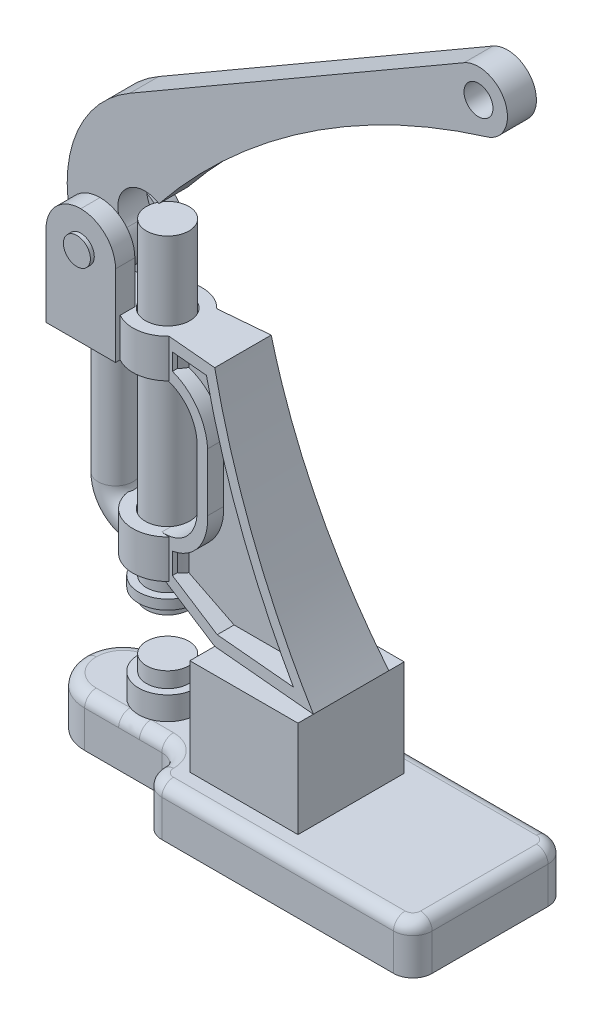
SolidWorks part; units mm, degrees
note: The reader was unsure of these and kept them because the rebuilt part matched: shared geometry of "Sketch8<2>".
other "Base Frame"
other "Sliding Rod"
other "Handle"
other "Pin"
ref_plane "Front Plane" through (0, 0, 0) normal (0, 0, 1) x (1, 0, 0)
ref_plane "Top Plane" through (0, 0, 0) normal (0, 1, 0) x (1, 0, 0)
ref_plane "Right Plane" through (0, 0, 0) normal (1, 0, 0) x (0, 0, -1)
sketch "Sketch1" plane through (0, 0, 0) normal (0, 1, 0) x (1, 0, 0)
  line L0 (-35, 20) -> (-105, 20)
  line L1 (-35, 40) -> (105, 40)
  line L2 (-35, 40) -> (-35, 20)
  line L3 (-35, -40) -> (105, -40)
  line L4 (105, 40) -> (105, -40)
  line L5 (-35, -20) -> (-105, -20)
  line L6 (-35, -20) -> (-35, -40)
  line L10 (-105, 20) -> (-105, -20)
  point P0 (0, 0)
  point P6 (-98.6874, 0)
  dimension "D1" = 70
  dimension "D2" = 140
  dimension "D3" = 40
  dimension "D4" = 40
  dimension "D5" = 80
  dimension "D6" = 35
  dimension "D7" = 20
extrude "Boss-Extrude1" add sketch "Sketch1" along normal blind 25
sketch "Sketch3" plane through (0, 25, 0) normal (0, 1, 0) x (1, 0, 0)
  line L0 (105, 40) -> (-35, 40) construction
  line L1 (-23, 27.5) -> (33, 27.5)
  line L2 (-23, 27.5) -> (-23, -27.5)
  line L3 (-23, -27.5) -> (33, -27.5)
  line L4 (33, 27.5) -> (33, -27.5)
  line L5 (-35, 40) -> (-35, 20) construction
  point P0 (0, 0)
  dimension "D1" = 56
  dimension "D2" = 55
  dimension "D3" = 12.5
  dimension "D4" = 12
extrude "Boss-Extrude2" add sketch "Sketch3" along normal blind 50
sketch "Sketch6" plane through (0, 0, 0) normal (0, 0, 1) x (1, 0, 0)
  line L0 (-23, 75) -> (-23, 200) construction
  line L1 (-23, 200) -> (-53, 200)
  line L2 (-53, 200) -> (-53, 180)
  line L3 (-53, 180) -> (-53, 110) construction
  line L4 (-33.0372, 161.2197) -> (-33.0372, 131.2197)
  line L5 (-53, 110) -> (-53, 90)
  line L6 (-53, 90) -> (-23, 75)
  line L7 (-23, 75) -> (33, 75)
  arc A0 (-23, 200) -> (33, 75) centre (327.5375, 281.9968) ccw
  arc A1 (-53, 180) -> (-33.0372, 161.2197) centre (-53, 160) cw
  arc A2 (-33.0372, 131.2197) -> (-53, 110) centre (-53, 130) cw
  dimension "D3" = 360
  dimension "D5" = 20
  dimension "D7" = 20
  dimension "D1" = 125
  dimension "D2" = 30
  dimension "D4" = 20
  dimension "D6" = 30
  dimension "D8" = 70
  dimension "D9" = 20
extrude "Boss-Extrude4" add sketch "Sketch6" along normal mid plane 24
sketch "Sketch7" plane through (0, 0, 12) normal (0, 0, 1) x (1, 0, 0)
  line L12 (-21.5836, 81) -> (21.6678, 81)
  line L13 (-27.7266, 194) -> (-47, 194)
  line L14 (-47, 194) -> (-47, 185.2982)
  line L15 (-27.0372, 161.3908) -> (-27.0372, 131.3908)
  line L16 (-47, 104.7018) -> (-47, 93.7082)
  line L17 (-47, 93.7082) -> (-21.5836, 81)
  line L18 (-21.5836, 81) -> (21.6678, 81)
  line L19 (-27.7266, 194) -> (-47, 194)
  line L20 (-47, 194) -> (-47, 185.2982)
  line L21 (-27.0372, 161.3908) -> (-27.0372, 131.3908)
  line L22 (-47, 104.7018) -> (-47, 93.7082)
  line L23 (-47, 93.7082) -> (-21.5836, 81)
  arc A6 (-27.7266, 194) -> (21.6678, 81) centre (327.5375, 281.9968) ccw
  arc A7 (-27.0372, 161.3908) -> (-47, 185.2982) centre (-53, 160) ccw
  arc A8 (-47, 104.7018) -> (-27.0372, 131.3908) centre (-53, 130) ccw
  arc A9 (-27.7266, 194) -> (21.6678, 81) centre (327.5375, 281.9968) ccw
  arc A10 (-27.0372, 161.3908) -> (-47, 185.2982) centre (-53, 160) ccw
  arc A11 (-47, 104.7018) -> (-27.0372, 131.3908) centre (-53, 130) ccw
  dimension "D1" = 6
extrude "Cut-Extrude1" cut sketch "Sketch7" against normal blind 6
mirror "Mirror2" about plane through (0, 0, 0) normal (0, 0, 1) of "Cut-Extrude1"
draft "Draft1" type of draft neutral plane draft angle 5 faces to draft 2 face at (-32.0851, 135.4883, -12) face at (-29.5218, 136.0106, 12) neutral plane through (-53, 200, 12) neutral plane normal (-1, 0, 0) parameters "D1"=5
sketch "Sketch8" plane through (0, 200, 0) normal (0, 1, 0) x (1, 0, 0)
  line L0 (-53, -12) -> (-53, 12) construction
  line L1 (-68.1623, 0) -> (85.9856, 0) construction
  circle A0 centre (-62, 0) radius 18
  dimension "D2" = 36
  dimension "D1" = 9
extrude "Boss-Extrude5" add sketch "Sketch8" against normal blind 20
extrude "Boss-Extrude6" add sketch "Sketch8<2>" against normal blind 20 from offset 90 offset against normal yes
sketch "Sketch8<2>" plane through (0, 200, 0) normal (0, 1, 0) x (1, 0, 0) same geometry as "Sketch8"
sketch "Sketch9" plane through (0, 200, 0) normal (0, 1, 0) x (1, 0, 0)
  line L0 (0, 0) -> (-100.5333, 0) construction
  line L1 (-107, 18) -> (-71, 18)
  line L2 (-107, 18) -> (-107, -18)
  line L3 (-107, -18) -> (-71, -18)
  line L4 (-71, 18) -> (-71, -18)
  point P0 (-91.6698, 0)
  dimension "D1" = 71
  dimension "D2" = 36
  dimension "D3" = 36
  dimension "D4" = 18
extrude "Boss-Extrude7" add sketch "Sketch9" against normal blind 20
sketch "Sketch10" plane through (0, 200, 0) normal (0, 1, 0) x (1, 0, 0)
  line L1 (-107, 18) -> (-71, 18)
  line L2 (-107, 18) -> (-107, 8)
  line L3 (-107, 8) -> (-71, 8)
  line L4 (-71, 18) -> (-71, 8)
  line L5 (-107, -18) -> (-71, -18)
  line L6 (-107, -18) -> (-107, -8)
  line L7 (-107, -8) -> (-71, -8)
  line L8 (-71, -18) -> (-71, -8)
  dimension "D1" = 10
  dimension "D2" = 10
extrude "Boss-Extrude8" add sketch "Sketch10" along normal blind 40
sketch "Sketch13" plane through (0, 200, 0) normal (0, 1, 0) x (1, 0, 0)
  point P0 (-62, 0)
hole_wizard "Ø22.0 (22) Diameter Hole1" positions "Sketch13" profile "Sketch12" hole size "Ø22.0" standard "DIN"
sketch "Sketch12" plane through (-62, 200, 0) normal (1, 0, 0) x (0, 0, 1)
  line L0 (0, 0) -> (0, 131.6095)
  line L1 (0, 131.6095) -> (11, 125)
  line L2 (11, 125) -> (11, 0)
  line L5 (11, 0) -> (0, 0)
  line L10 (0, 131.6095) -> (-11, 125) construction
  line L11 (0, -6.35) -> (0, 107.95) construction
  dimension "Hole Dia." = 22
  dimension "Hole Depth" = 125
  dimension "Drill Angle" = 118
sketch "Sketch16" plane through (0, 0, 18) normal (0, 0, 1) x (1, 0, 0)
  line L0 (-107, 240) -> (-71, 240) construction
  line L1 (-107, 180) -> (-107, 240) construction
  point P0 (-89, 222)
  dimension "D1" = 18
  dimension "D2" = 18
hole_wizard "Ø14.0 (14) Diameter Hole1" positions "Sketch16" profile "Sketch15" hole size "Ø14.0" standard "DIN" end condition through all
sketch "Sketch15" plane through (-89, 222, 18) normal (1, 0, 0) x (0, -1, 0)
  line L0 (0, 0) -> (0, 58)
  line L1 (0, 58) -> (7, 58)
  line L2 (7, 58) -> (7, 0)
  line L5 (7, 0) -> (0, 0)
  line L11 (0, -6.35) -> (0, 107.95) construction
  dimension "Thru Hole Dia." = 14
  dimension "Thru Hole Depth" = 58
sketch "Sketch20" plane through (0, 200, 0) normal (0, 1, 0) x (1, 0, 0)
  circle A0 centre (-62, 0) radius 11 construction
  circle A1 centre (-62, 0) radius 11
extrude "Boss-Extrude10" add sketch "Sketch20" along normal blind 40 and the other way blind 130 separate body
sketch "Sketch21" plane through (0, 0, 0) normal (0, 0, 1) x (1, 0, 0)
  line L0 (-74.1099, 293.9816) -> (98.9691, 394.1996)
  circle A0 centre (-89, 222) radius 7 construction
  circle A1 centre (-89, 222) radius 7
  arc A2 (-103.2383, 217.2807) -> (-77.2638, 231.3414) centre (-89, 222) ccw
  arc A3 (-77.2638, 231.3414) -> (-59, 252) centre (-66.31, 240.06) cw
  arc A4 (-59, 252) -> (110.4332, 366.7475) centre (213.4051, 32.2377) cw
  arc A5 (-103.2383, 217.2807) -> (-74.1099, 293.9816) centre (-41.5391, 237.7309) cw
  arc A6 (98.9691, 394.1996) -> (110.4332, 366.7475) centre (106.4854, 381.2187) cw
  circle A7 centre (106.4854, 381.2187) radius 7.5
  dimension "D1" = 30
  dimension "D4" = 65
  dimension "D5" = 14
  dimension "D6" = 350
  dimension "D7" = 200
  dimension "D8" = 15
  dimension "D9" = 15
  dimension "D2" = 30
  dimension "D3" = 30
extrude "Boss-Extrude11" add sketch "Sketch21" along normal mid plane 15 separate body
sketch "Sketch22" plane through (0, 25, 0) normal (0, 1, 0) x (1, 0, 0)
  circle A2 centre (-62, 0) radius 15
  circle A3 centre (-62, 0) radius 15
  dimension "D1" = 4
extrude "Boss-Extrude12" add sketch "Sketch22" along normal blind 12
sketch "Sketch24" plane through (0, 37, 0) normal (0, 1, 0) x (1, 0, 0)
  circle A2 centre (-62, 0) radius 11
  circle A3 centre (-62, 0) radius 11
  dimension "D1" = 4
extrude "Boss-Extrude13" add sketch "Sketch24" along normal blind 8
sketch "Sketch25" plane through (0, 0, 18) normal (0, 0, 1) x (1, 0, 0)
  circle A0 centre (-89, 222) radius 7 construction
  circle A1 centre (-89, 222) radius 7
extrude "Boss-Extrude14" add sketch "Sketch25" against normal blind 40 from offset 2 separate body
sketch "Sketch26" plane through (0, 0, 0) normal (0, 0, 1) x (1, 0, 0)
  line L0 (-89, 180) -> (-89, 113)
  line L1 (-107, 180) -> (-71, 180) construction
  line L2 (-74, 98) -> (-73.9, 98)
  arc A0 (-89, 113) -> (-74, 98) centre (-74, 113) ccw
  point P6 (0, 0)
  point P7 (0, 0)
  point P9 (0, 0)
  point P10 (0, 0)
  point P11 (0, 0)
  point P12 (-74, 98)
  dimension "D2" = 15
  dimension "D1" = 67
  dimension "D3" = 0.1
sketch "Sketch44" plane through (0, 180, 0) normal (0, -1, 0) x (1, 0, 0)
  circle A0 centre (-89, 0) radius 9
  dimension "D1" = 18
sweep "Sweep1" add profiles "Sketch44" path "Sketch26"
fillet "Fillet1" radius 20 2 edges at (-105, 12.5, -20) (-105, 12.5, 20)
fillet "Fillet2" radius 18 4 edges at (-71, 240, 13) (-107, 240, 13) (-71, 240, -13) (-107, 240, -13)
fillet "Fillet3" radius 10 6 edges at (-35, 12.5, -20) (-35, 12.5, -40) (105, 12.5, -40) (105, 12.5, 40) (-35, 12.5, 40) (-35, 12.5, 20)
fillet "Fillet4" radius 6 13 edges at (102.0711, 25, -37.0711) (105, 25, 0) (102.0711, 25, 37.0711) (35, 25, 40) (-32.0711, 25, 37.0711) (-37.9289, 25, 22.9289) (-65, 25, 20) (-99.1421, 25, 14.1421) (-99.1421, 25, -14.1421) (-65, 25, -20) (-37.9289, 25, -22.9289) (-32.0711, 25, -37.0711) (35, 25, -40)
sketch "Sketch45" plane through (0, 200, 0) normal (0, 1, 0) x (1, 0, 0)
  circle A0 centre (-62, 0) radius 11.5
  dimension "D1" = 23
extrude "Cut-Extrude2" cut sketch "Sketch45" against normal blind 123
sketch "Sketch46" plane through (0, 70, 0) normal (0, -1, 0) x (1, 0, 0)
  circle A0 centre (-62, 0) radius 15
  dimension "D1" = 30
extrude "Boss-Extrude15" add sketch "Sketch46" against normal blind 5 from offset 5 offset against normal yes
other "Save Bodies1"
